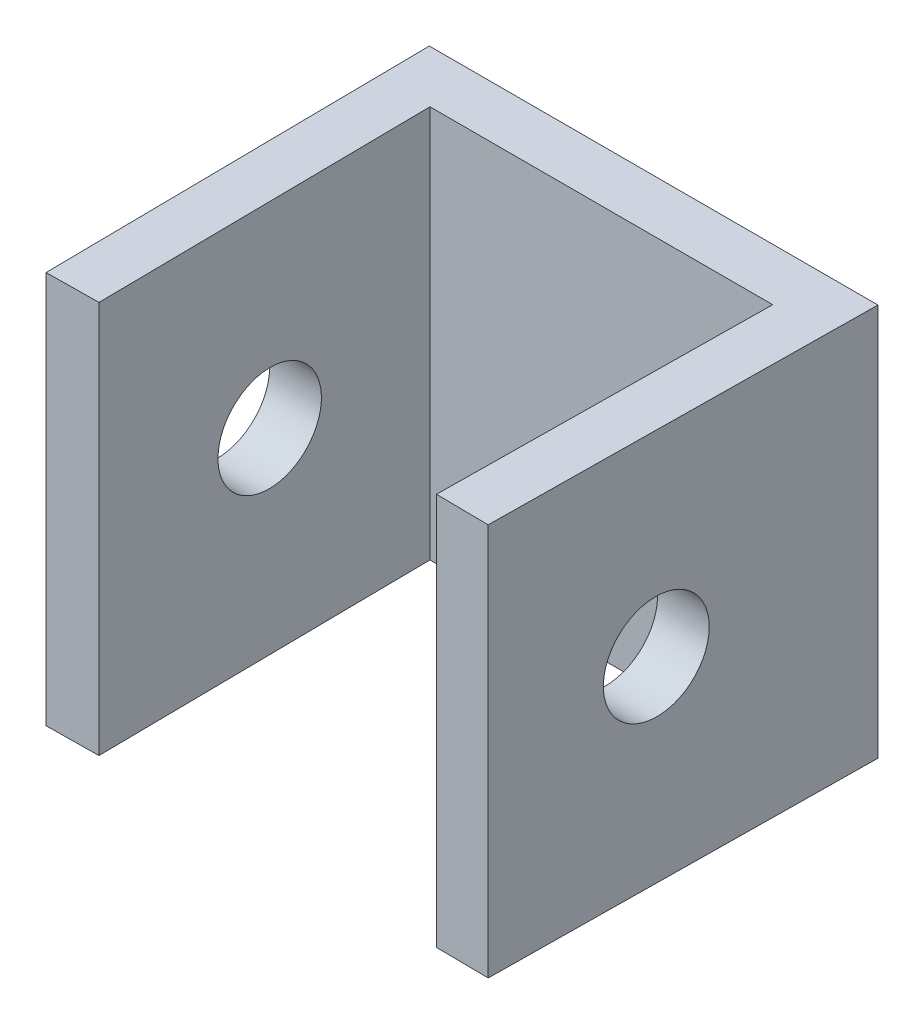
SolidWorks part; units mm, degrees
ref_plane "Front Plane" through (0, 0, 0) normal (0, 0, 1) x (1, 0, 0)
ref_plane "Top Plane" through (0, 0, 0) normal (0, 1, 0) x (1, 0, 0)
ref_plane "Right Plane" through (0, 0, 0) normal (1, 0, 0) x (0, 0, -1)
sketch "Sketch1" plane through (0, 0, 0) normal (0, 1, 0) x (1, 0, 0)
  line L0 (-12.8, -12.8) -> (-13.1, 12.8)
  line L1 (-12.8, 12.8) -> (12.8, 12.8) construction
  line L2 (-12.8, 12.8) -> (-12.8, -12.8) construction
  line L4 (12.8, 12.8) -> (12.8, -12.6) construction
  line L5 (-13.1, 12.8) -> (13.1, 12.8)
  line L6 (13.1, 12.8) -> (12.8, -12.6)
  line L7 (-16.7997, -12.8469) -> (-17.1471, 16.8)
  line L8 (-17.1471, 16.8) -> (17.1475, 16.8)
  line L9 (17.1475, 16.8) -> (16.7997, -12.6472)
  line L11 (-16.7997, -12.8469) -> (-12.8, -12.8)
  line L12 (12.8, -12.6) -> (16.7997, -12.6472)
  dimension "D1" = 25.6
  dimension "D2" = 25.4
  dimension "D3" = 0.3
  dimension "D4" = 0.3
  dimension "D5" = 4
extrude "Boss-Extrude1" add sketch "Sketch1" along normal blind 30
sketch "Sketch2" plane through (0, 30, 0) normal (0, 1, 0) x (1, 0, 0)
  line L0 (0.0002, 16.8) -> (0.0002, 30.8112) construction
  line L1 (17.1475, 16.8) -> (-17.1471, 16.8) construction
  line L2 (0.0002, 36.8) -> (-4.0998, 36.8) construction
  line L3 (0.0002, 36.8) -> (2.1002, 36.8) construction
  line L4 (-4.0998, 36.8) -> (-4.0998, 23.7851)
  line L5 (-2.0998, 36.8) -> (-2.0998, 23.7851)
  line L6 (-11.0849, 16.8) -> (-5.4334, 16.8)
  line L7 (-4.0998, 36.8) -> (-2.0998, 36.8)
  line L8 (4.1002, 36.8) -> (2.1002, 36.8)
  line L9 (11.0853, 16.8) -> (5.4337, 16.8)
  line L10 (2.1002, 36.8) -> (2.1002, 23.7851)
  line L11 (4.1002, 36.8) -> (4.1002, 23.7851)
  arc A0 (-4.0998, 23.7851) -> (-11.0849, 16.8) centre (-11.0849, 23.7851) cw
  arc A1 (-2.0998, 23.7851) -> (-5.4334, 16.8) centre (-11.0849, 23.7851) cw
  arc A2 (-2.0998, 23.7851) -> (-11.0849, 14.8) centre (-11.0849, 23.7851) cw construction
  arc A3 (4.1002, 23.7851) -> (11.0853, 16.8) centre (11.0853, 23.7851) ccw
  arc A4 (2.1002, 23.7851) -> (5.4337, 16.8) centre (11.0853, 23.7851) ccw
  dimension "D1" = 20
  dimension "D2" = 4.1
  dimension "D3" = 2
sketch "Sketch3" plane through (16.9467, 0, 0.2002) normal (0.9999, 0, 0.0118) x (0.0118, 0, -0.9999)
  line L0 (-12.448, 0) -> (12.952, 0) construction
  line L1 (0.252, 0) -> (0.252, 30) construction
  line L5 (-12.448, 30) -> (17.0013, 30) construction
  circle A0 centre (0.252, 15) radius 4
  dimension "D1" = 12.7
extrude "Cut-Extrude1" cut sketch "Sketch3" against normal blind 40
sketch "Sketch4" plane through (0, 0, -16.8) normal (0, 0, -1) x (-1, 0, 0)
  line L0 (17.1471, 0) -> (-17.1475, 30) construction
  line L1 (-0.0002, 15) -> (10.9998, 15) construction
  line L2 (10.9998, -5.5) -> (10.9998, 35.5)
  line L3 (10.9998, 35.5) -> (13.9998, 35.5)
  line L4 (10.9998, -5.5) -> (13.9998, -5.5)
  line L6 (13.9998, 35.5) -> (13.9998, -5.5)
  point P8 (10.9998, 15)
  dimension "D1" = 3
extrude "Boss-Extrude2" add sketch "Sketch4" against normal blind 4
sketch "Sketch5" plane through (0, 0, -16.8) normal (0, 0, -1) x (-1, 0, 0)
  line L1 (13.9998, 35.5) -> (13.9998, 43.25)
  line L11 (10.9998, 35.5) -> (10.9998, 43.25)
  line L17 (10.9998, 35.5) -> (13.9998, 35.5)
  line L18 (10.9998, 43.25) -> (13.9998, 43.25)
  line L21 (17.1471, 15) -> (-23.8791, 15) construction
  line L22 (17.1471, 30) -> (17.1471, 0) construction
  line L23 (10.9998, -13.25) -> (13.9998, -13.25)
  line L24 (10.9998, -5.5) -> (13.9998, -5.5)
  line L25 (10.9998, -5.5) -> (10.9998, -13.25)
  line L26 (13.9998, -5.5) -> (13.9998, -13.25)
extrude "Boss-Extrude3" add sketch "Sketch5" against normal blind 4 and the other way blind 25
sketch "Sketch6" plane through (-13.9998, 0, 0) normal (-1, 0, 0) x (0, 0, 1)
  line L0 (-16.8, 43.25) -> (-16.8, -13.25)
  line L1 (-41.8, 43.25) -> (-12.8, 43.25) construction
  line L2 (-12.8, -13.25) -> (-12.8, 43.25)
  line L3 (-12.8, -13.25) -> (-16.8, -13.25)
  line L4 (-12.8, 43.25) -> (-16.8, 43.25)
extrude "Boss-Extrude4" add sketch "Sketch6" along normal up to surface (3.1005 mm away) up to face at (-16.9087, 15, 3.5485)
sketch "Sketch7" plane through (-16.9479, 0, 0.1986) normal (-0.9999, 0, 0.0117) x (0.0117, 0, 0.9999)
  line L0 (12.6491, 30) -> (-40.2558, 30)
  line L1 (-40.2558, 30) -> (-53.5662, 38.8911)
  line L2 (-53.5662, 38.8911) -> (-52.1927, 50.0279)
  line L3 (-52.1927, 50.0279) -> (-13.8033, 48.7791)
  line L4 (-13.8033, 48.7791) -> (23.5061, 46.0536)
  line L5 (23.5061, 46.0536) -> (14.6716, 30)
  line L6 (14.6716, 30) -> (12.6491, 30)
  line L7 (12.6491, 0) -> (-49.961, 0)
  line L8 (-49.961, 0) -> (-43.2107, -24.3317)
  line L9 (-43.2107, -24.3317) -> (11.6534, -25.8063)
  line L10 (11.6534, -25.8063) -> (35.291, -15.9344)
  line L11 (35.291, -15.9344) -> (29.6892, -2.5212)
  line L12 (29.6892, -2.5212) -> (12.6491, 0)
extrude "Cut-Extrude2" cut sketch "Sketch7" against normal blind 62
